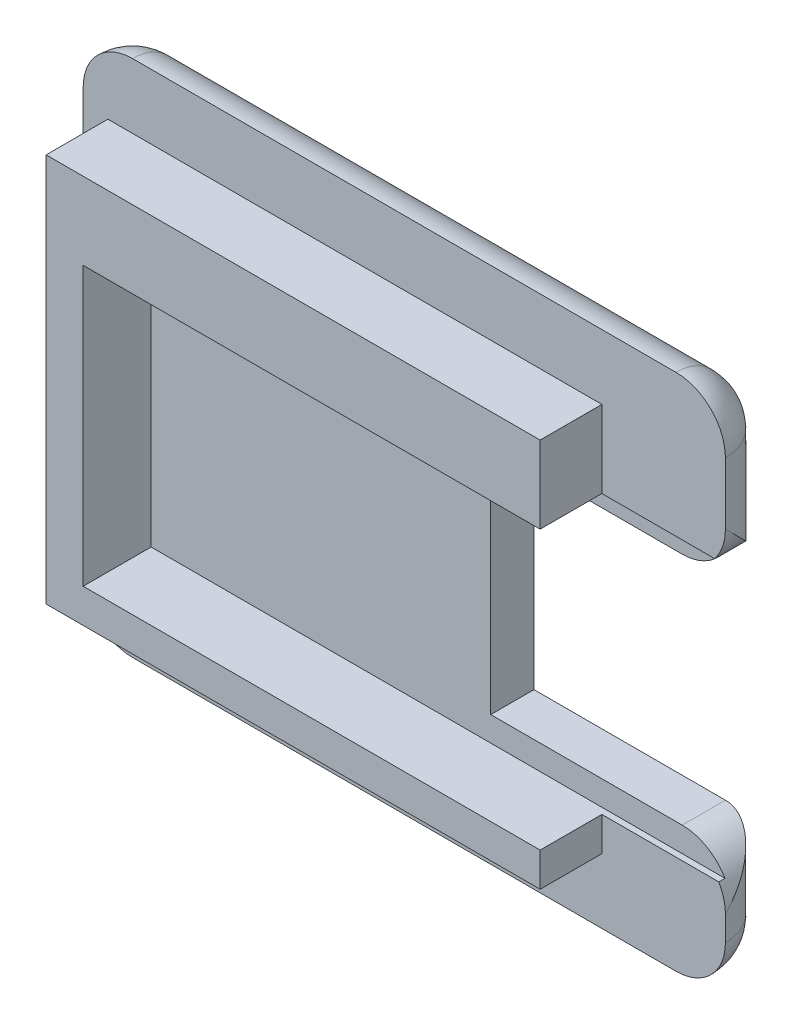
SolidWorks part; units mm, degrees
material "Plain Carbon Steel"
ref_plane "Front Plane" through (0, 0, 0) normal (0, 0, 1) x (1, 0, 0)
ref_plane "Top Plane" through (0, 0, 0) normal (0, 1, 0) x (1, 0, 0)
ref_plane "Right Plane" through (0, 0, 0) normal (1, 0, 0) x (0, 0, -1)
sketch "Sketch1" plane through (0, 0, 0) normal (0, 0, 1) x (1, 0, 0)
  line L1 (-26, 21) -> (26, 21)
  line L2 (-26, 21) -> (-26, -21)
  line L3 (-26, -21) -> (26, -21)
  line L4 (26, 21) -> (26, -21)
  line L5 (-26, 21) -> (26, -21) construction
  line L6 (-26, -21) -> (26, 21) construction
  point P0 (0, 0)
  dimension "D1" = 42
  dimension "D2" = 52
extrude "Boss-Extrude1" add sketch "Sketch1" along normal blind 4
sketch "Sketch2" plane through (0, 0, 4) normal (0, 0, 1) x (1, 0, 0)
  line L0 (26, 21) -> (-26, 21) construction
  line L1 (-24, 15.75) -> (16, 15.75)
  line L2 (-24, 15.75) -> (-24, -15.75)
  line L3 (-24, -15.75) -> (16, -15.75)
  line L4 (16, 15.75) -> (16, -15.75)
  line L5 (-24, 15.75) -> (16, -15.75) construction
  line L6 (-24, -15.75) -> (16, 15.75) construction
  line L7 (-26, -21) -> (26, -21) construction
  line L8 (26, -21) -> (26, 21) construction
  dimension "D1" = 10
  dimension "D2" = 40
  dimension "D3" = 5.25
  dimension "5" = 5.25
extrude "Boss-Extrude2" add sketch "Sketch2" along normal blind 5
sketch "Sketch4" plane through (0, 0, 9) normal (0, 0, 1) x (1, 0, 0)
  line L0 (-26, 21) -> (-26, -21) construction
  line L1 (-21, 9.5) -> (29, 9.5)
  line L2 (-21, 9.5) -> (-21, -13)
  line L3 (-21, -13) -> (29, -13)
  line L4 (29, 9.5) -> (29, -13)
  line L5 (-21, 9.5) -> (29, -13) construction
  line L6 (-21, -13) -> (29, 9.5) construction
  line L8 (-26, -21) -> (26, -21) construction
  line L11 (26, 21) -> (-26, 21) construction
  point P0 (0, 0)
  dimension "D1" = 11.5
  dimension "D2" = 5
  dimension "D3" = 8
  dimension "D4" = 50
extrude "Cut-Extrude2" cut sketch "Sketch4" against normal blind 5.5
sketch "Sketch5" plane through (0, 0, 3.5) normal (0, 0, 1) x (1, 0, 0)
  line L1 (6.5, 8) -> (26, 8)
  line L2 (6.5, 8) -> (6.5, -11)
  line L3 (6.5, -11) -> (26, -11)
  line L4 (26, 8) -> (26, -11)
  line L5 (6.5, 8) -> (26, -11) construction
  line L6 (6.5, -11) -> (26, 8) construction
  line L7 (16, 9.5) -> (-21, 9.5) construction
  line L8 (-21, -13) -> (26, -13) construction
  line L9 (26, -13) -> (26, 9.5) construction
  point P0 (14.4273, 2.716)
  dimension "D1" = 19
  dimension "D2" = 19.5
  dimension "D3" = 1.5
  dimension "D4" = 2
extrude "Cut-Extrude3" cut sketch "Sketch5" against normal blind 10
fillet "Fillet2" radius 4 11 edges at (26, -16, 0) (26, 14.5, 0) (26, 8, 1.75) (26, -11, 1.75) (26, -21, 2) (-26, -21, 2) (0, -21, 0) (-26, 0, 0) (0, 21, 0) (-26, 21, 2) (26, 21, 2)
